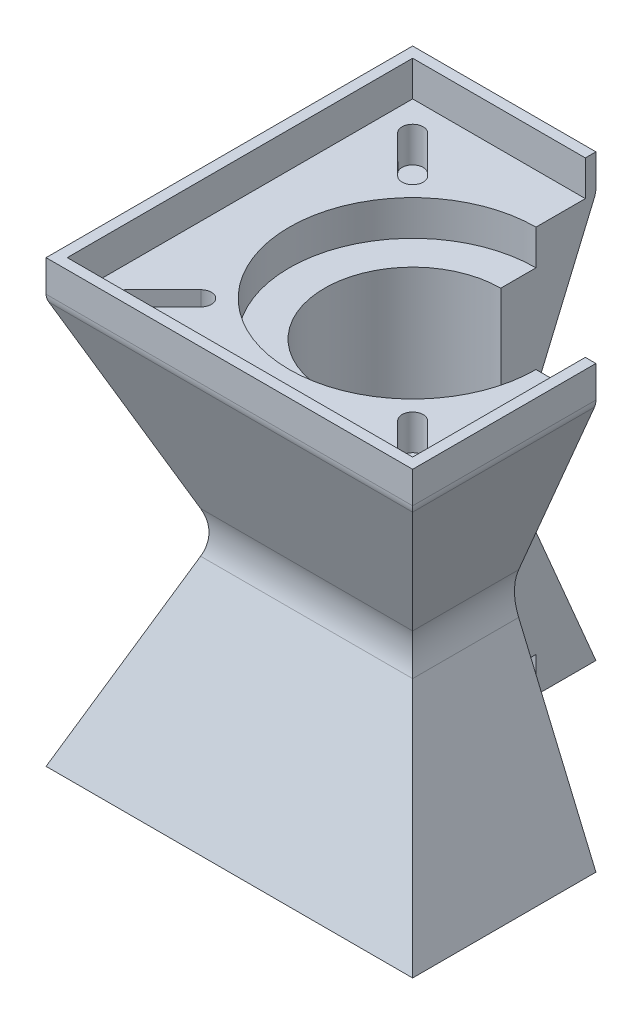
SolidWorks part; units mm, degrees
material "Cast Stainless Steel"
ref_plane "Front Plane" through (0, 0, 0) normal (0, 0, 1) x (1, 0, 0)
ref_plane "Top Plane" through (0, 0, 0) normal (0, 1, 0) x (1, 0, 0)
ref_plane "Right Plane" through (0, 0, 0) normal (1, 0, 0) x (0, 0, -1)
sketch "Sketch1" plane through (0, 0, 0) normal (0, 1, 0) x (1, 0, 0)
  line L1 (-52, 52) -> (52, 52)
  line L2 (-52, 52) -> (-52, -52)
  line L3 (-52, -52) -> (52, -52)
  line L4 (52, 52) -> (52, -52)
  line L5 (-52, 52) -> (52, -52) construction
  line L6 (-52, -52) -> (52, 52) construction
  circle A0 centre (0, 0) radius 25
  point P0 (0, 0)
  dimension "D2" = 50
  dimension "D1" = 104
  dimension "D3" = 104
extrude "Boss-Extrude1" add sketch "Sketch1" against normal blind 57.5 draft 23 contours L2 L1 L4 L3
ref_plane "Plane1" through (0, -57.5, 0) normal (0, 1, 0) x (1, 0, 0)
extrude "Cut-Extrude1" cut sketch "Sketch1<3>" against normal through all contours A0 region at (0, 0, 0)
sketch "Sketch1<3>" plane through (0, 0, 0) normal (0, 1, 0) x (1, 0, 0) same geometry as "Sketch1"
sketch "Sketch3" plane through (0, 0, 0) normal (0, 1, 0) x (1, 0, 0)
  circle A0 centre (0, 0) radius 35
  dimension "D1" = 70
extrude "Cut-Extrude2" cut sketch "Sketch3" against normal blind 10
mirror "Mirror2" about plane through (0, -57.5, 0) normal (0, 1, 0) of "Cut-Extrude2", "Cut-Extrude1", "Boss-Extrude1"
sketch "Sketch4" plane through (0, 0, 0) normal (0, 1, 0) x (1, 0, 0)
  line L1 (0, 0) -> (95.5565, 0)
  line L2 (0, 0) -> (0, 88.4669)
  line L3 (0, 88.4669) -> (95.5565, 88.4669)
  line L4 (95.5565, 0) -> (95.5565, 88.4669)
extrude "Cut-Extrude3" cut sketch "Sketch4" against normal through all
fillet "Fillet1" radius 15 4 edges at (-13.7963, -57.5, -27.5927) (-27.5927, -57.5, 0) (27.5927, -57.5, 13.7963) (0, -57.5, 27.5927)
sketch "Sketch5" plane through (0, 0, 0) normal (0, 1, 0) x (1, 0, 0)
  line L0 (-49, 49) -> (-49, -49)
  line L1 (-49, -49) -> (49, -49)
  line L2 (49, -49) -> (49, -3)
  line L5 (-3, 49) -> (-49, 49)
  line L6 (0, 35) -> (0, 52)
  line L7 (0, 52) -> (-52, 52)
  line L8 (-52, 52) -> (-52, -52)
  line L9 (-52, -52) -> (52, -52)
  line L10 (52, -52) -> (52, 0)
  line L11 (52, 0) -> (35, 0)
  line L13 (0, 52) -> (-52, 52)
  line L14 (-52, 52) -> (-52, -52)
  line L15 (-52, -52) -> (52, -52)
  line L16 (52, -52) -> (52, 0)
  line L18 (49, -3) -> (37.8814, -3) construction
  line L19 (52, 0) -> (35, 0) construction
  line L20 (-3, 37.8814) -> (-3, 49) construction
  line L21 (0, 35) -> (0, 52) construction
  line L22 (49, -3) -> (49, 0)
  line L23 (35, 0) -> (52, 0) construction
  line L24 (49, 0) -> (52, 0)
  line L25 (-3, 49) -> (0, 49)
  line L26 (0, 52) -> (0, 35) construction
  line L27 (0, 49) -> (0, 52)
  arc A1 (0, 35) -> (35, 0) centre (0, 0) ccw
  arc A3 (0, 35) -> (35, 0) centre (0, 0) ccw construction
  arc A4 (-3, 37.8814) -> (37.8814, -3) centre (0, 0) ccw construction
  dimension "D1" = 0
  dimension "D2" = 3
extrude "Boss-Extrude2" add sketch "Sketch5" along normal blind 10
fillet "Fillet2" radius 5 4 edges at (-26, 0, -52) (-52, 0, 0) (0, 0, 52) (52, 0, 26)
sketch "Sketch6" plane through (0, 0, 0) normal (0, 1, 0) x (1, 0, 0)
  line L0 (-40.6586, -40.6586) -> (-30.052, -30.052) construction
  line L1 (-42.78, -38.5373) -> (-32.1734, -27.9307)
  line L2 (-38.5373, -42.78) -> (-27.9307, -32.1734)
  line L3 (-30.052, -30.052) -> (0, 0) construction
  line L5 (0, 0) -> (-52, 0) construction
  line L6 (-52, 52) -> (-52, -52) construction
  line L8 (-40.6586, 40.6586) -> (-30.052, 30.052) construction
  line L14 (-38.5373, 42.78) -> (-27.9307, 32.1734)
  line L15 (-42.78, 38.5373) -> (-32.1734, 27.9307)
  line L18 (-40.6586, -40.6586) -> (-49, -49) construction
  line L21 (40.6586, -40.6586) -> (30.052, -30.052) construction
  line L22 (38.5373, -42.78) -> (27.9307, -32.1734)
  line L23 (42.78, -38.5373) -> (32.1734, -27.9307)
  line L24 (0, 0) -> (-40.6586, -40.6586) construction
  line L25 (0, 0) -> (-40.6586, 40.6586) construction
  line L29 (40.6586, 40.6586) -> (30.052, 30.052) construction
  line L30 (42.78, 38.5373) -> (32.1734, 27.9307)
  line L31 (38.5373, 42.78) -> (27.9307, 32.1734)
  line L32 (40.6586, 40.6586) -> (30.052, 30.052) construction
  line L33 (42.78, 38.5373) -> (32.1734, 27.9307)
  line L34 (38.5373, 42.78) -> (27.9307, 32.1734)
  arc A0 (-42.78, -38.5373) -> (-38.5373, -42.78) centre (-40.6586, -40.6586) ccw
  arc A1 (-27.9307, -32.1734) -> (-32.1734, -27.9307) centre (-30.052, -30.052) ccw
  arc A9 (-38.5373, 42.78) -> (-42.78, 38.5373) centre (-40.6586, 40.6586) ccw
  arc A10 (-32.1734, 27.9307) -> (-27.9307, 32.1734) centre (-30.052, 30.052) ccw
  circle A11 centre (0, 0) radius 50 construction
  arc A14 (38.5373, -42.78) -> (42.78, -38.5373) centre (40.6586, -40.6586) ccw
  arc A15 (32.1734, -27.9307) -> (27.9307, -32.1734) centre (30.052, -30.052) ccw
  arc A20 (42.78, 38.5373) -> (38.5373, 42.78) centre (40.6586, 40.6586) ccw
  arc A21 (27.9307, 32.1734) -> (32.1734, 27.9307) centre (30.052, 30.052) ccw
  point P2 (-35.3553, -35.3553)
  point P12 (35.3553, 35.3553)
  point P20 (-35.3553, 35.3553)
  point P26 (0, 0)
  point P27 (0, 0)
  point P35 (35.3553, -35.3553)
  point P52 (35.3553, 35.3553)
  point P59 (35.3553, 35.3553)
  dimension "D2" = 3
  dimension "D3" = 100
  dimension "D1" = 15
  dimension "D4" = 4
  dimension "D5" = 90
  dimension "D6" = 57.5
extrude "Cut-Extrude4" cut sketch "Sketch6" against normal blind 10
mirror "Mirror3" about plane through (0, -57.5, 0) normal (0, 1, 0) of "Cut-Extrude4"
